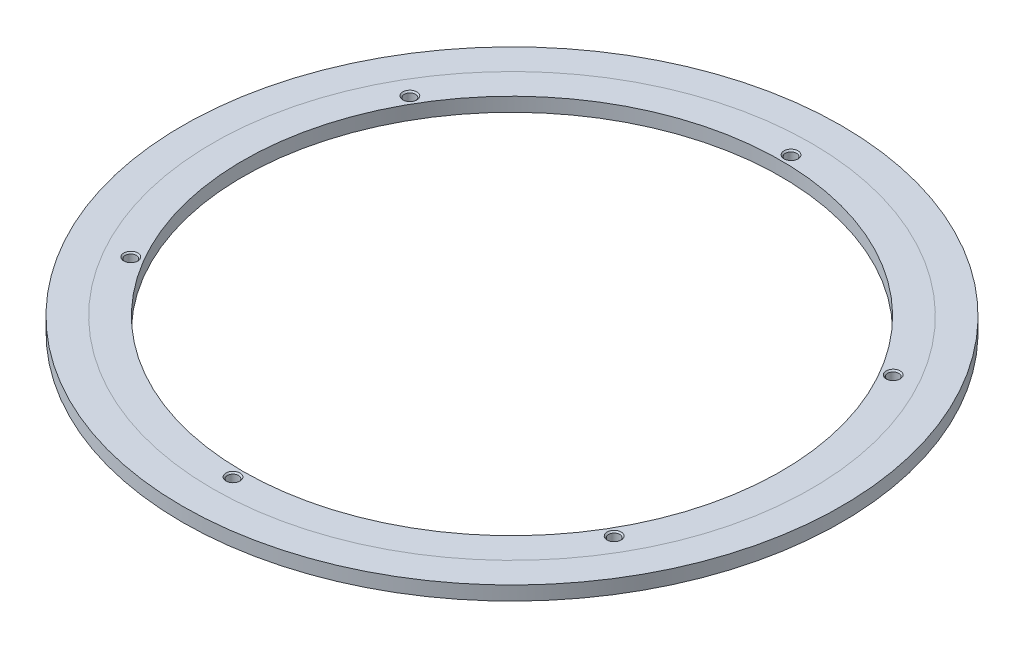
SolidWorks part; units mm, degrees
ref_plane "Front Plane" through (0, 0, 0) normal (0, 0, 1) x (1, 0, 0)
ref_plane "Top Plane" through (0, 0, 0) normal (0, 1, 0) x (1, 0, 0)
ref_plane "Right Plane" through (0, 0, 0) normal (1, 0, 0) x (0, 0, -1)
sketch "Sketch1" plane through (0, 0, 0) normal (0, 1, 0) x (1, 0, 0)
  line L0 (-122.5, 0) -> (-150, 0) construction
  circle A0 centre (0, 0) radius 122.5
  circle A1 centre (0, 0) radius 150
  circle A2 centre (0, 0) radius 136.25
  point P7 (-136.25, 0)
  dimension "D1" = 245
  dimension "D2" = 300
extrude "Boss-Extrude1" add sketch "Sketch1" against normal blind 6.35 contours A2 A1 region at (-145.7574, 0, 0)
extrude "Boss-Extrude2" add sketch "Sketch1<3>" against normal blind 6.35 separate body contours A0 A2 region at (-132.3963, 0, 0)
sketch "Sketch1<3>" plane through (0, 0, 0) normal (0, 1, 0) x (1, 0, 0) same geometry as "Sketch1"
sketch "Sketch2" plane through (0, 0, 0) normal (0, 1, 0) x (1, 0, 0)
  circle A0 centre (0, 0) radius 127
  point P5 (0, 127)
  point P9 (109.9852, 63.5)
  point P10 (109.9852, -63.5)
  point P11 (0, -127)
  point P12 (-109.9852, -63.5)
  point P13 (-109.9852, 63.5)
  point P15 (-109.977, 63.5142)
  point P16 (-110.29, -62.9692)
  dimension "D1" = 254
  dimension "D2" = 6
hole_wizard "#10 Clearance Hole1" positions "Sketch2" profile "Sketch3" hole size "#10" standard "ANSI Inch" end condition up to next
sketch "Sketch3" plane through (-109.9852, 0, -63.5) normal (1, 0, 0) x (0, 0, 1)
  line L0 (0, 0) -> (0, 6.35)
  line L1 (0, 6.35) -> (3.1877, 6.35)
  line L2 (2.5527, 5.715) -> (2.5527, 0.635)
  line L3 (2.5527, 0.635) -> (3.1877, 0)
  line L5 (3.1877, 0) -> (0, 0)
  line L6 (-2.5527, 0.635) -> (-3.1877, 0) construction
  line L7 (3.1877, 6.35) -> (2.5527, 5.715)
  line L8 (-3.1877, 6.35) -> (-2.5527, 5.715) construction
  line L11 (0, -6.35) -> (0, 107.95) construction
  dimension "Thru Hole Dia." = 5.1054
  dimension "Thru Hole Depth" = 6.35
  dimension "Near C'Sink Dia." = 6.3754
  dimension "Near C'Sink Angle" = 90
  dimension "Far C'Sink Dia." = 6.3754
  dimension "Far C'Sink Angle" = 90
